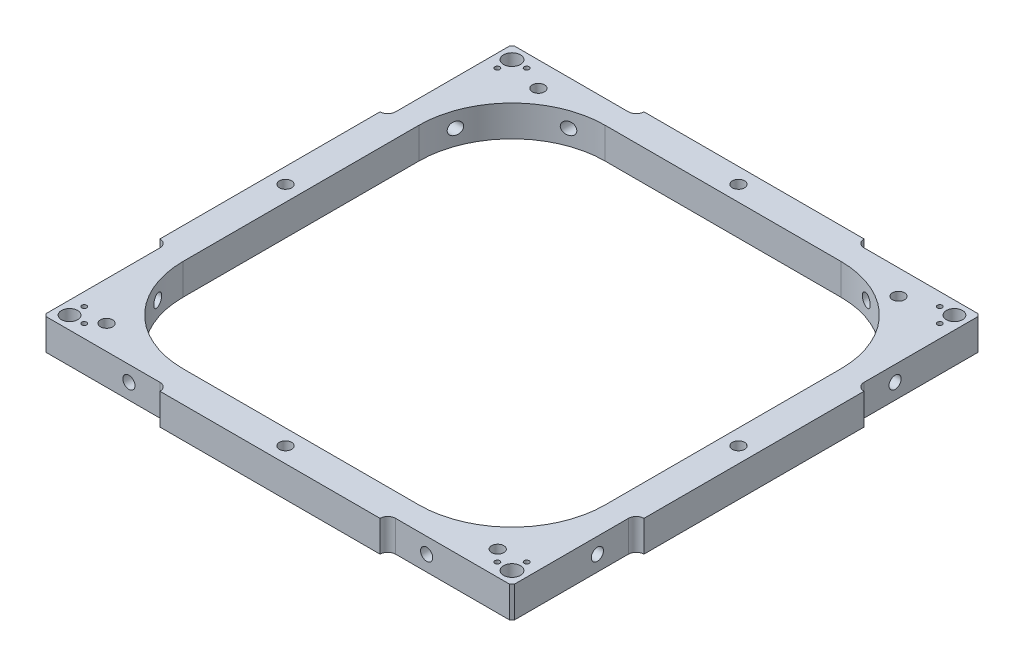
SolidWorks part; units mm, degrees
material "6061-T6 (SS)"
ref_plane "Front Plane" through (0, 0, 0) normal (0, 0, 1) x (1, 0, 0)
ref_plane "Top Plane" through (0, 0, 0) normal (0, 1, 0) x (1, 0, 0)
ref_plane "Right Plane" through (0, 0, 0) normal (1, 0, 0) x (0, 0, -1)
sketch "Sketch1" plane through (0, 0, 0) normal (0, 1, 0) x (1, 0, 0)
  line L0 (-49.5, 22.5125) -> (-47.9125, 22.5125)
  line L1 (-49.5, -49.5) -> (49.5, -49.5)
  line L2 (-49.5, -49.5) -> (-49.5, 49.5)
  line L3 (-49.5, 49.5) -> (49.5, 49.5)
  line L4 (49.5, -49.5) -> (49.5, 49.5)
  line L5 (-49.5, -49.5) -> (49.5, 49.5) construction
  line L6 (-49.5, 49.5) -> (49.5, -49.5) construction
  line L7 (-47.9125, 22.5125) -> (-47.9125, 47.9125)
  line L8 (-47.9125, 47.9125) -> (-22.5125, 47.9125)
  line L9 (-22.5125, 47.9125) -> (-22.5125, 49.5)
  line L10 (22.5125, 49.5) -> (22.5125, 47.9125)
  line L11 (22.5125, 47.9125) -> (47.9125, 47.9125)
  line L12 (47.9125, 47.9125) -> (47.9125, 22.5125)
  line L13 (47.9125, 22.5125) -> (49.5, 22.5125)
  line L14 (49.5, -22.5125) -> (47.9125, -22.5125)
  line L15 (47.9125, -22.5125) -> (47.9125, -47.9125)
  line L16 (47.9125, -47.9125) -> (22.5125, -47.9125)
  line L17 (22.5125, -47.9125) -> (22.5125, -49.5)
  line L18 (-22.5125, -49.5) -> (-22.5125, -47.9125)
  line L19 (-22.5125, -47.9125) -> (-47.9125, -47.9125)
  line L20 (-47.9125, -47.9125) -> (-47.9125, -22.5125)
  line L21 (-47.9125, -22.5125) -> (-49.5, -22.5125)
  point P0 (0, 0)
  dimension "D1" = 99
  dimension "D2" = 99
  dimension "D3" = 26.9875
  dimension "D4" = 1.5875
  dimension "D5" = 26.9875
  dimension "D6" = 1.5875
extrude "Boss-Extrude1" add sketch "Sketch1" along normal blind 6.35 contours L21 L20 L19 L18 L1 L17 L16 L15 L14 L4 L13 L12 L11 L10 L3 L9 L8 L7 L0 L2 region at (0, 0, 0)
chamfer "Chamfer1" distance 0.508 angle 45 4 edges at (47.9125, 3.175, -47.9125) (-47.9125, 3.175, -47.9125) (-47.9125, 3.175, 47.9125) (47.9125, 3.175, 47.9125)
fillet "Fillet1" radius 1.5875 8 edges at (-47.9125, 3.175, -22.5125) (-22.5125, 3.175, -47.9125) (22.5125, 3.175, -47.9125) (47.9125, 3.175, -22.5125) (47.9125, 3.175, 22.5125) (22.5125, 3.175, 47.9125) (-22.5125, 3.175, 47.9125) (-47.9125, 3.175, 22.5125)
hole_wizard "M4x0.7 Tapped Hole1" positions "Sketch2" profile "Sketch3" tap size "M4x0.7" standard "ANSI Metric" end condition through all
sketch "Sketch2" plane through (0, 0, 0) normal (0, -1, 0) x (-1, 0, 0)
  line L0 (-49.5, -22.5125) -> (-49.5, 22.5125) construction
  line L1 (22.5125, 49.5) -> (-22.5125, 49.5) construction
  line L5 (49.5, -22.5125) -> (49.5, 22.5125) construction
  line L6 (22.5125, -49.5) -> (-22.5125, -49.5) construction
  point P0 (-45.25, 45.25)
  point P4 (45.25, -45.25)
  dimension "D1" = 4.25
  dimension "D2" = 4.25
  dimension "D5" = 4.25
  dimension "D6" = 4.25
sketch "Sketch3" plane through (45.25, 0, -45.25) normal (1, 0, 0) x (0, 0, -1)
  line L0 (0, 0) -> (0, 6.35)
  line L1 (0, 6.35) -> (1.65, 6.35)
  line L2 (1.65, 6.35) -> (1.65, 0)
  line L5 (1.65, 0) -> (0, 0)
  line L11 (0, -6.35) -> (0, 107.95) construction
  dimension "Thru Tap Drill Dia." = 3.3
  dimension "Thru Tap Drill Depth" = 6.35
cosmetic thread "Hole Thread8" parameters "D2"=4
cosmetic thread "Hole Thread9" parameters "D2"=4
hole_wizard "M3x0.5 Tapped Hole1" positions "Sketch6" profile "Sketch7" tap size "M3x0.5" standard "ANSI Metric"
sketch "Sketch6" plane through (0, 0, 47.9125) normal (0, 0, 1) x (1, 0, 0)
  line L1 (-24.1, 0) -> (-47.4045, 0) construction
  line L4 (47.4045, 0) -> (24.1, 0) construction
  line L5 (-24.1, 0) -> (-24.1, 6.35) construction
  line L7 (24.1, 6.35) -> (24.1, 0) construction
  point P0 (-30.45, 3.175)
  point P2 (30.45, 3.175)
  dimension "D1" = 6.35
  dimension "D2" = 3.175
  dimension "D3" = 6.35
  dimension "D4" = 3.175
sketch "Sketch7" plane through (-30.45, 3.175, 47.9125) normal (1, 0, 0) x (0, -1, 0)
  line L0 (0, 0) -> (0, 8.3711)
  line L1 (0, 8.3711) -> (1.25, 7.62)
  line L2 (1.25, 7.62) -> (1.25, 0)
  line L5 (1.25, 0) -> (0, 0)
  line L10 (0, 8.3711) -> (-1.25, 7.62) construction
  line L11 (0, -6.35) -> (0, 107.95) construction
  dimension "Tap Drill Dia." = 2.5
  dimension "Tap Drill Depth" = 7.62
  dimension "Drill Angle" = 118
cosmetic thread "Hole Thread1" parameters "D1"=4.7625, "D2"=3
cosmetic thread "Hole Thread2" parameters "D1"=4.7625, "D2"=3
ref_plane "Plane1" through (0, 0, 0) normal (0, 0, 1) x (1, 0, 0)
ref_plane "Plane2" through (0, 0, 0) normal (-1, 0, 0) x (0, 0, 1)
ref_axis "Axis1" through (0, -0.3175, 0) along (0, 1, 0)
pattern_circular "CirPattern1" count 4 over 360 about axis through (0, -0.3175, 0) along (0, 1, 0) of "M3x0.5 Tapped Hole1"
sketch "Sketch9" plane through (0, 6.35, 0) normal (0, 1, 0) x (1, 0, 0)
  line L0 (0, 3.4925) -> (0, -3.4925) construction
  line L1 (-3.4925, 0) -> (3.4925, 0) construction
  circle A0 centre (-40.005, -42.926) radius 0.7937
  circle A1 centre (40.005, -42.926) radius 0.7937
  circle A2 centre (36.195, 42.8625) radius 0.7937
  circle A3 centre (-37.465, 42.8625) radius 0.7937
  dimension "D7" = 1.5875
  dimension "D1" = 40.005
  dimension "D2" = 40.005
  dimension "D3" = 2.54
  dimension "D4" = 73.66
  dimension "D5" = 42.8625
  dimension "D6" = 42.926
extrude "Cut-Extrude2" cut sketch "Sketch9" against normal through all
sketch "Sketch11" plane through (0, 6.35, 0) normal (0, 1, 0) x (1, 0, 0)
  line L0 (-22.5125, 49.5) -> (22.5125, 49.5) construction
  line L1 (-43.15, -43.15) -> (43.15, -43.15)
  line L2 (-43.15, -43.15) -> (-43.15, 43.15)
  line L3 (-43.15, 43.15) -> (43.15, 43.15)
  line L4 (43.15, -43.15) -> (43.15, 43.15)
  line L5 (-43.15, -43.15) -> (43.15, 43.15) construction
  line L6 (-43.15, 43.15) -> (43.15, -43.15) construction
  line L7 (49.5, -22.5125) -> (49.5, 22.5125) construction
  line L8 (-44.2725, 42.0275) -> (42.0275, -44.2725)
  line L9 (-42.0275, -44.2725) -> (44.2725, 42.0275)
  line L10 (-42.0275, 44.2725) -> (44.2725, -42.0275)
  line L11 (-44.2725, -42.0275) -> (42.0275, 44.2725)
  circle A5 centre (-37.465, 42.8625) radius 3.9687
  circle A6 centre (-37.465, 42.8625) radius 3.9687
  circle A9 centre (36.195, 42.8625) radius 3.9687
  circle A10 centre (36.195, 42.8625) radius 3.9687
  circle A12 centre (-40.005, -42.926) radius 3.9688
  circle A13 centre (-40.005, -42.926) radius 3.9687
  circle A14 centre (0, 0) radius 25.4
  circle A15 centre (40.005, -42.926) radius 3.9688
  circle A16 centre (40.005, -42.926) radius 3.9687
  circle A17 centre (0, 0) radius 22.225
  point P0 (0, 0)
  dimension "D9" = 50.8
  dimension "D1" = 6.35
  dimension "D2" = 6.35
  dimension "D3" = 3.175
  dimension "D4" = 3.175
  dimension "D5" = 3.175
  dimension "D6" = 3.175
  dimension "D7" = 1.5875
  dimension "D8" = 1.5875
  dimension "D10" = 3.175
hole_wizard "M3x0.5 Tapped Hole3" positions "Sketch14" profile "Sketch15" tap size "M3x0.5" standard "ANSI Metric"
sketch "Sketch14" plane through (0, 6.35, 0) normal (0, 1, 0) x (1, 0, 0)
  line L0 (0, 3.4925) -> (0, -3.4925) construction
  line L1 (-22.5125, -49.5) -> (22.5125, -49.5) construction
  point P0 (0, -46.325)
  dimension "D1" = 3.175
sketch "Sketch15" plane through (0, 6.35, 46.325) normal (1, 0, 0) x (0, 0, 1)
  line L0 (0, 0) -> (0, 8.3711)
  line L1 (0, 8.3711) -> (1.25, 7.62)
  line L2 (1.25, 7.62) -> (1.25, 0)
  line L5 (1.25, 0) -> (0, 0)
  line L10 (0, 8.3711) -> (-1.25, 7.62) construction
  line L11 (0, -6.35) -> (0, 107.95) construction
  dimension "Tap Drill Dia." = 2.5
  dimension "Tap Drill Depth" = 7.62
  dimension "Drill Angle" = 118
cosmetic thread "Hole Thread5" parameters "D1"=6.096, "D2"=3
sketch "Sketch16" plane through (0, 6.35, 0) normal (0, 1, 0) x (1, 0, 0)
  line L0 (-22.5125, 49.5) -> (22.5125, 49.5) construction
  line L1 (-43.15, -43.15) -> (43.15, -43.15)
  line L2 (-43.15, -43.15) -> (-43.15, 43.15)
  line L3 (-43.15, 43.15) -> (43.15, 43.15)
  line L4 (43.15, -43.15) -> (43.15, 43.15)
  line L5 (-43.15, -43.15) -> (43.15, 43.15) construction
  line L6 (-43.15, 43.15) -> (43.15, -43.15) construction
  line L7 (49.5, -22.5125) -> (49.5, 22.5125) construction
  arc A0 (24.1, 43.15) -> (43.15, 24.1) centre (24.1, 24.1) cw
  arc A1 (43.15, -24.1) -> (24.1, -43.15) centre (24.1, -24.1) cw
  arc A2 (-24.1, -43.15) -> (-43.15, -24.1) centre (-24.1, -24.1) cw
  arc A3 (-43.15, 24.1) -> (-24.1, 43.15) centre (-24.1, 24.1) cw
  circle A4 centre (36.195, 42.8625) radius 3.2731 construction
  circle A5 centre (36.195, 42.8625) radius 0.7937 construction
  point P0 (0, 0)
  dimension "D3" = 19.05
  dimension "D1" = 6.35
  dimension "D2" = 6.35
extrude "Cut-Extrude3" cut sketch "Sketch16" against normal through all contours A3 L2 A2 L1 A1 L4 A0 L3 region at (0, 6.35, 0)
pattern_circular "CirPattern2" count 4 over 360 about axis through (0, -0.3175, 0) along (0, 1, 0) of "M3x0.5 Tapped Hole3"
sketch "Sketch17" plane through (0, 6.35, 0) normal (0, 1, 0) x (1, 0, 0)
  circle A0 centre (-37.465, 42.8625) radius 3.25
  circle A1 centre (36.195, 42.8625) radius 3.25
  circle A2 centre (40.005, -42.926) radius 3.25
  circle A3 centre (-40.005, -42.926) radius 3.25
  dimension "D1" = 6.5
  dimension "D2" = 6.5
  dimension "D3" = 6.5
  dimension "D4" = 6.5
hole_wizard "#8-36 Tapped Hole1" positions "Sketch18" profile "Sketch19" tap size "#8-36" standard "ANSI Inch" end condition through all
sketch "Sketch18" plane through (0, 6.35, 0) normal (0, 1, 0) x (1, 0, 0)
  line L0 (-22.5125, 49.5) -> (22.5125, 49.5) construction
  line L1 (-49.5, -22.5125) -> (-49.5, 22.5125) construction
  line L2 (-22.5125, -49.5) -> (22.5125, -49.5) construction
  line L3 (49.5, -22.5125) -> (49.5, 22.5125) construction
  point P0 (-45.25, 45.25)
  point P2 (45.25, -45.25)
  dimension "D1" = 4.25
  dimension "D2" = 4.25
  dimension "D3" = 4.25
  dimension "D4" = 4.25
sketch "Sketch19" plane through (-45.25, 6.35, -45.25) normal (1, 0, 0) x (0, 0, 1)
  line L0 (0, 0) -> (0, 6.35)
  line L1 (0, 6.35) -> (1.7272, 6.35)
  line L2 (1.7272, 6.35) -> (1.7272, 0)
  line L5 (1.7272, 0) -> (0, 0)
  line L11 (0, -6.35) -> (0, 107.95) construction
  dimension "Thru Tap Drill Dia." = 3.4544
  dimension "Thru Tap Drill Depth" = 6.35
cosmetic thread "Hole Thread6" parameters "D2"=4.1656
cosmetic thread "Hole Thread7" parameters "D2"=4.1656
hole_wizard "M3x0.5 Tapped Hole4" positions "Sketch20" profile "Sketch21" tap size "M3x0.5" standard "ANSI Metric" end condition through all
sketch "Sketch20" plane through (0, 6.35, 0) normal (0, 1, 0) x (1, 0, 0)
  point P0 (36.195, 42.8625)
  point P3 (-37.465, 42.8625)
  point P6 (-40.005, -42.926)
  point P9 (40.005, -42.926)
sketch "Sketch21" plane through (36.195, 6.35, -42.8625) normal (1, 0, 0) x (0, 0, 1)
  line L0 (0, 0) -> (0, 6.35)
  line L1 (0, 6.35) -> (1.25, 6.35)
  line L2 (1.25, 6.35) -> (1.25, 0)
  line L5 (1.25, 0) -> (0, 0)
  line L11 (0, -6.35) -> (0, 107.95) construction
  dimension "Thru Tap Drill Dia." = 2.5
  dimension "Thru Tap Drill Depth" = 6.35
cosmetic thread "Hole Thread10" parameters "D2"=3
cosmetic thread "Hole Thread11" parameters "D2"=3
cosmetic thread "Hole Thread12" parameters "D2"=3
cosmetic thread "Hole Thread13" parameters "D2"=3
sketch "Sketch22" plane through (0, 6.35, 0) normal (0, 1, 0) x (1, 0, 0)
  line L0 (45.25, 45.25) -> (45.25, 42.25) construction
  line L1 (45.25, 45.25) -> (42.25, 45.25) construction
  circle A0 centre (45.25, 42.25) radius 0.5
  circle A1 centre (42.25, 45.25) radius 0.5
  dimension "D2" = 1
  dimension "D3" = 1
  dimension "D1" = 3
extrude "Cut-Extrude4" cut sketch "Sketch22" against normal through all
pattern_circular "CirPattern3" count 4 over 360 about axis through (0, -0.3175, 0) along (0, 1, 0) of "Cut-Extrude4"
